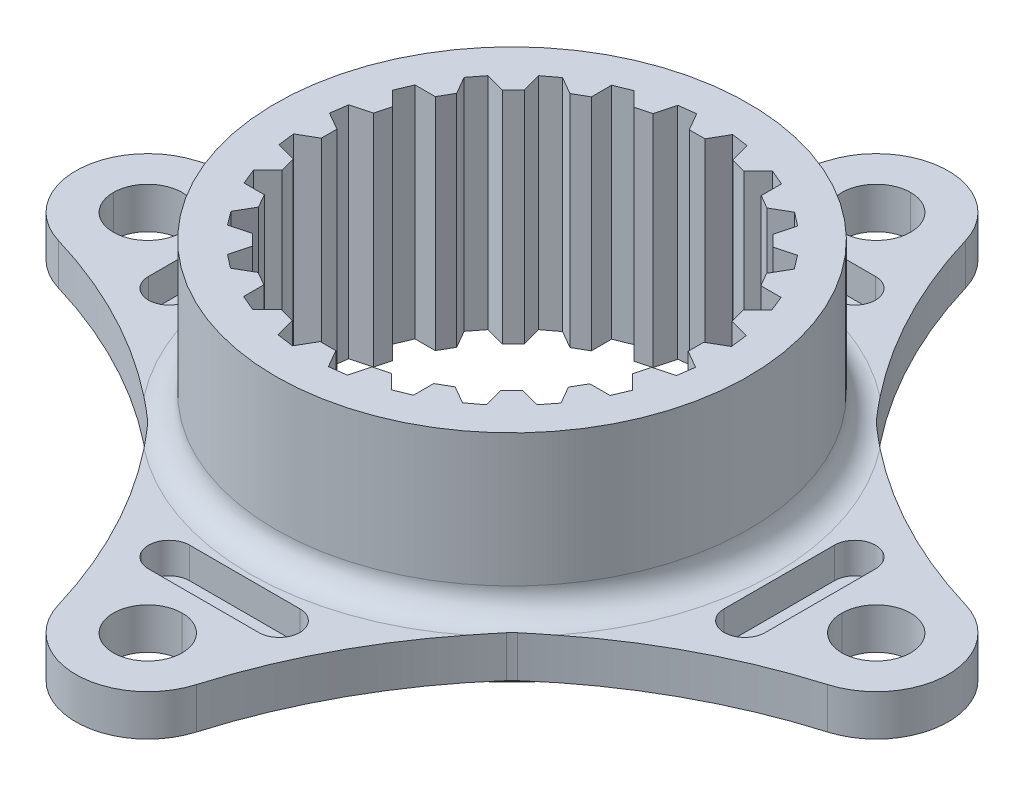
SolidWorks part; units mm, degrees
note: '?' marks a value the reader was unsure of. The reader was unsure of these and kept them because the rebuilt part matched: shared geometry of "Sketch6<5>".
material "7075-T6 (SN)"
ref_plane "Front Plane" through (0, 0, 0) normal (0, 0, 1) x (1, 0, 0)
ref_plane "Top Plane" through (0, 0, 0) normal (0, 1, 0) x (1, 0, 0)
ref_plane "Right Plane" through (0, 0, 0) normal (1, 0, 0) x (0, 0, -1)
sketch "Sketch1" plane through (0, 0, 0) normal (0, 1, 0) x (1, 0, 0)
  line L0 (274.6284, 454.6081) -> (780.6456, 454.6081) construction
  circle A0 centre (0, 0) radius 23
  dimension "D1" = 46
sketch "Sketch5" plane through (0, 0, 0) normal (0, 1, 0) x (1, 0, 0)
  circle A0 centre (0, 0) radius 23
  circle A1 centre (0, 0) radius 25
  dimension "D1" = 46
  dimension "D2" = 50
sketch "Sketch6" plane through (0, 0, 0) normal (0, 1, 0) x (1, 0, 0)
  line L0 (-0.9689, -22.7363) -> (0.9689, -22.7363)
  line L1 (0.9689, -22.7363) -> (2.2189, -24.9013)
  line L2 (0, 33.3652) -> (0, -36.4848) construction
  line L3 (-0.9689, -22.7363) -> (-2.2189, -24.9013)
  line L4 (-4.9456, -22.1943) -> (-4.2985, -24.6091)
  line L5 (-6.8174, -21.6927) -> (-4.9456, -22.1943)
  line L6 (-6.8174, -21.6927) -> (-8.5852, -23.4605)
  line L7 (-10.5182, -22.6399) -> (-8.5852, -23.4605)
  line L8 (-10.5182, -20.1399) -> (-10.5182, -22.6399)
  line L9 (-12.1965, -19.171) -> (-10.5182, -20.1399)
  line L10 (-12.1965, -19.171) -> (-14.3615, -20.421)
  line L11 (-16.0164, -19.1281) -> (-14.3615, -20.421)
  line L12 (-15.3693, -16.7133) -> (-16.0164, -19.1281)
  line L13 (-16.7396, -15.343) -> (-15.3693, -16.7133)
  line L14 (-16.7396, -15.343) -> (-19.1544, -15.99)
  line L15 (-20.4182, -14.3129) -> (-19.1544, -15.99)
  line L16 (-19.1682, -12.1478) -> (-20.4182, -14.3129)
  line L17 (-20.1372, -10.4696) -> (-19.1682, -12.1478)
  line L18 (-20.1372, -10.4696) -> (-22.6372, -10.4696)
  line L19 (-23.4239, -8.5225) -> (-22.6372, -10.4696)
  line L20 (-21.6561, -6.7547) -> (-23.4239, -8.5225)
  line L21 (-22.1576, -4.8829) -> (-21.6561, -6.7547)
  line L22 (-22.1576, -4.8829) -> (-24.5725, -4.2358)
  line L23 (-24.8284, -2.1515) -> (-24.5725, -4.2358)
  line L24 (-22.6633, -0.9015) -> (-24.8284, -2.1515)
  line L25 (-22.6633, 1.0364) -> (-22.6633, -0.9015)
  line L26 (-22.6633, 1.0364) -> (-24.8284, 2.2864)
  line L27 (-24.5361, 4.366) -> (-24.8284, 2.2864)
  line L28 (-22.1213, 5.013) -> (-24.5361, 4.366)
  line L29 (-21.6197, 6.8849) -> (-22.1213, 5.013)
  line L30 (-21.6197, 6.8849) -> (-23.3875, 8.6526)
  line L31 (-22.567, 10.5857) -> (-23.3875, 8.6526)
  line L32 (-20.067, 10.5857) -> (-22.567, 10.5857)
  line L33 (-19.098, 12.2639) -> (-20.067, 10.5857)
  line L34 (-19.098, 12.2639) -> (-20.348, 14.429)
  line L35 (-19.0552, 16.0838) -> (-20.348, 14.429)
  line L36 (-16.6403, 15.4368) -> (-19.0552, 16.0838)
  line L37 (-15.27, 16.8071) -> (-16.6403, 15.4368)
  line L38 (-15.27, 16.8071) -> (-15.9171, 19.2219)
  line L39 (-14.24, 20.4857) -> (-15.9171, 19.2219)
  line L40 (-12.0749, 19.2357) -> (-14.24, 20.4857)
  line L41 (-10.3966, 20.2046) -> (-12.0749, 19.2357)
  line L42 (-10.3966, 20.2046) -> (-10.3966, 22.7046)
  line L43 (-8.4496, 23.4913) -> (-10.3966, 22.7046)
  line L44 (-6.6818, 21.7235) -> (-8.4496, 23.4913)
  line L45 (-4.8099, 22.2251) -> (-6.6818, 21.7235)
  line L46 (-4.8099, 22.2251) -> (-4.1629, 24.6399)
  line L47 (-2.0785, 24.8958) -> (-4.1629, 24.6399)
  line L48 (-0.8285, 22.7308) -> (-2.0785, 24.8958)
  line L49 (1.1093, 22.7308) -> (-0.8285, 22.7308)
  line L50 (1.1093, 22.7308) -> (2.3593, 24.8958)
  line L51 (4.4389, 24.6036) -> (2.3593, 24.8958)
  line L52 (5.086, 22.1888) -> (4.4389, 24.6036)
  line L53 (6.9578, 21.6872) -> (5.086, 22.1888)
  line L54 (6.9578, 21.6872) -> (8.7256, 23.455)
  line L55 (10.6586, 22.6344) -> (8.7256, 23.455)
  line L56 (10.6586, 20.1344) -> (10.6586, 22.6344)
  line L57 (12.3369, 19.1655) -> (10.6586, 20.1344)
  line L58 (12.3369, 19.1655) -> (14.5019, 20.4155)
  line L59 (16.1568, 19.1226) -> (14.5019, 20.4155)
  line L60 (15.5097, 16.7078) -> (16.1568, 19.1226)
  line L61 (16.88, 15.3375) -> (15.5097, 16.7078)
  line L62 (16.88, 15.3375) -> (19.2948, 15.9845)
  line L63 (20.5586, 14.3074) -> (19.2948, 15.9845)
  line L64 (19.3086, 12.1424) -> (20.5586, 14.3074)
  line L65 (20.2776, 10.4641) -> (19.3086, 12.1424)
  line L66 (20.2776, 10.4641) -> (22.7776, 10.4641)
  line L67 (23.5643, 8.517) -> (22.7776, 10.4641)
  line L68 (21.7965, 6.7492) -> (23.5643, 8.517)
  line L69 (22.298, 4.8774) -> (21.7965, 6.7492)
  line L70 (22.298, 4.8774) -> (24.7129, 4.2303)
  line L71 (24.9688, 2.146) -> (24.7129, 4.2303)
  line L72 (22.8037, 0.896) -> (24.9688, 2.146)
  line L73 (22.8037, -1.0419) -> (22.8037, 0.896)
  line L74 (22.8037, -1.0419) -> (24.9688, -2.2919)
  line L75 (24.6765, -4.3714) -> (24.9688, -2.2919)
  line L76 (22.2617, -5.0185) -> (24.6765, -4.3714)
  line L77 (21.7601, -6.8903) -> (22.2617, -5.0185)
  line L78 (21.7601, -6.8903) -> (23.5279, -8.6581)
  line L79 (22.7074, -10.5912) -> (23.5279, -8.6581)
  line L80 (20.2074, -10.5912) -> (22.7074, -10.5912)
  line L81 (19.2384, -12.2694) -> (20.2074, -10.5912)
  line L82 (19.2384, -12.2694) -> (20.4884, -14.4345)
  line L83 (19.1955, -16.0893) -> (20.4884, -14.4345)
  line L84 (16.7807, -15.4423) -> (19.1955, -16.0893)
  line L85 (15.4104, -16.8126) -> (16.7807, -15.4423)
  line L86 (15.4104, -16.8126) -> (16.0575, -19.2274)
  line L87 (14.3804, -20.4912) -> (16.0575, -19.2274)
  line L88 (12.2153, -19.2412) -> (14.3804, -20.4912)
  line L89 (10.537, -20.2101) -> (12.2153, -19.2412)
  line L90 (10.537, -20.2101) -> (10.537, -22.7101)
  line L91 (8.59, -23.4968) -> (10.537, -22.7101)
  line L92 (6.8222, -21.729) -> (8.59, -23.4968)
  line L93 (4.9503, -22.2306) -> (6.8222, -21.729)
  line L94 (4.9503, -22.2306) -> (4.3033, -24.6454)
  line L95 (2.2189, -24.9013) -> (4.3033, -24.6454)
  line L96 (-4.2985, -24.6091) -> (-2.2189, -24.9013)
  circle A0 centre (0, 0) radius 23 construction
  circle A1 centre (0, 0) radius 25 construction
  point P11 (0, -23)
  point P131 (0.0702, -0.0027)
  dimension "D4" = 2.5
  dimension "D1" = 2.1
  dimension "D5" = 112
  dimension "D6" = 120
  dimension "D2" = 1.9379
  dimension "D3" = 24
sketch "Sketch8" plane through (0, 0, 0) normal (0, 1, 0) x (1, 0, 0)
  circle A0 centre (0, 0) radius 100
  dimension "D1" = 200
extrude "Boss-Extrude4" add sketch "Sketch8" along normal blind 24.638 contours A0
extrude "Cut-Extrude1" cut sketch "Sketch6" along normal through all
sketch "Sketch9" plane through (0, 24.638, 0) normal (0, 1, 0) x (1, 0, 0)
  circle A0 centre (0, 0) radius 29.21
  dimension "D1" = 58.42
extrude "Cut-Extrude3" cut sketch "Sketch9" against normal blind 19.558 flip side to cut
sketch "Sketch10" plane through (0, 5.08, 0) normal (0, 1, 0) x (1, 0, 0)
  circle A1 centre (0, 45) radius 4.2545
  circle A4 centre (45, 0) radius 4.2545
  circle A5 centre (0, -45) radius 4.2545
  circle A6 centre (-45, 0) radius 4.2545
  point P11 (0, 0)
  point P28 (0, 0)
  dimension "D1" = 4
  dimension "D2" = 8.509
  dimension "D3" = 45
sketch "Sketch11" plane through (0, 5.08, 0) normal (0, 1, 0) x (1, 0, 0)
  line L0 (0, 45) -> (45, 0) construction
  line L1 (0, 0) -> (70.7107, 70.7107) construction
  line L2 (0, 45) -> (8.89, 45) construction
  line L3 (0, 45) -> (8.5239, 47.5249) construction
  circle A0 centre (0, 0) radius 100 construction
  arc A1 (8.5239, 47.5249) -> (22.5, 22.5) centre (71.1118, 66.0643) ccw
  arc A2 (47.5249, 8.5239) -> (22.5, 22.5) centre (66.0643, 71.1118) cw
  arc A3 (47.5249, -8.5239) -> (22.5, -22.5) centre (66.0643, -71.1118) ccw
  arc A4 (-8.5239, -47.5249) -> (-22.5, -22.5) centre (-71.1118, -66.0643) ccw
  arc A5 (-47.5249, 8.5239) -> (-22.5, 22.5) centre (-66.0643, 71.1118) ccw
  arc A6 (8.5239, -47.5249) -> (22.5, -22.5) centre (71.1118, -66.0643) cw
  arc A7 (-47.5249, -8.5239) -> (-22.5, -22.5) centre (-66.0643, -71.1118) cw
  circle A8 centre (0, 45) radius 8.89
  circle A9 centre (45, 0) radius 8.89
  circle A10 centre (0, -45) radius 8.89
  circle A11 centre (-45, 0) radius 8.89
  arc A12 (-8.5239, 47.5249) -> (-22.5, 22.5) centre (-71.1118, 66.0643) cw
  point P15 (0, 0)
  point P31 (0, 0)
  point P37 (0, 0)
  point P42 (0, 0)
  point P51 (0, 0)
  dimension "D4" = 4
  dimension "D1" = 4
  dimension "D2" = 17.78
  dimension "D5" = 4
  dimension "D3" = 16.5
extrude "Cut-Extrude6" cut sketch "Sketch11" against normal blind 7.62
extrude "Cut-Extrude7" cut sketch "Sketch10" against normal blind 7.62
fillet "Fillet2" radius 3.175 1 edges at (0, 5.08, 29.21)
ref_plane "Plane1" through (0, 0, 0) normal (0, 0, 1) x (1, 0, 0)
ref_plane "Plane2" through (0, 0, 0) normal (-1, 0, 0) x (0, 0, 1)
split line "Split Line1"
split line "Split Line2"
ref_axis "Axis1" through (0, 5.334, 0) along (0, -1, 0)?
fillet "Fillet3" radius 7.62 4 edges at (-22.5, 2.5654, -22.5) (22.5, 2.5654, -22.5) (22.5, 2.5654, 22.5) (-22.5, 2.5654, 22.5)
sketch "Sketch13" plane through (0, 5.08, 0) normal (0, 1, 0) x (1, 0, 0)
  line L0 (0, 2.794) -> (0, -2.794) construction
  line L1 (-8.4262, 38.1) -> (8.4262, 38.1)
  line L2 (-8.4262, 38.1) -> (-10.795, 33.02)
  line L3 (-10.795, 33.02) -> (10.795, 33.02)
  line L4 (8.4262, 38.1) -> (10.795, 33.02)
  point P11 (0, 33.02)
  dimension "D1" = 115
  dimension "D2" = 115
  dimension "D3" = 5.08
  dimension "D4" = 0
  dimension "D5" = 21.59
  dimension "D6" = 33.02
extrude "Cut-Extrude12" cut sketch "Sketch13" against normal blind 3.81 contours L1 L4 L3 L2
fillet "Fillet5" radius 2.54 4 edges at (-10.795, 3.175, -33.02) (10.795, 3.175, -33.02) (-8.4262, 3.175, -38.1) (8.4262, 3.175, -38.1)
pattern_circular "CirPattern1" count 4 over 360 about axis through (0, 0, 0) along (0, 1, 0) of "Cut-Extrude12", "Fillet5"
sketch "Sketch14" plane through (0, 0, 0) normal (0, -1, 0) x (1, 0, 0)
  circle A0 centre (0, 0) radius 29.0322
  dimension "D1" = 58.0644
extrude "Boss-Extrude5" add sketch "Sketch14" along normal blind 2.54
extrude "Cut-Extrude17" cut sketch "Sketch6<5>" against normal blind 2.54
sketch "Sketch6<5>" plane through (0, 0, 0) normal (0, 1, 0) x (1, 0, 0) same geometry as "Sketch6"
chamfer "Chamfer1" distance 0.508 angle 45 1 edges at (0, -2.54, -29.0322)
